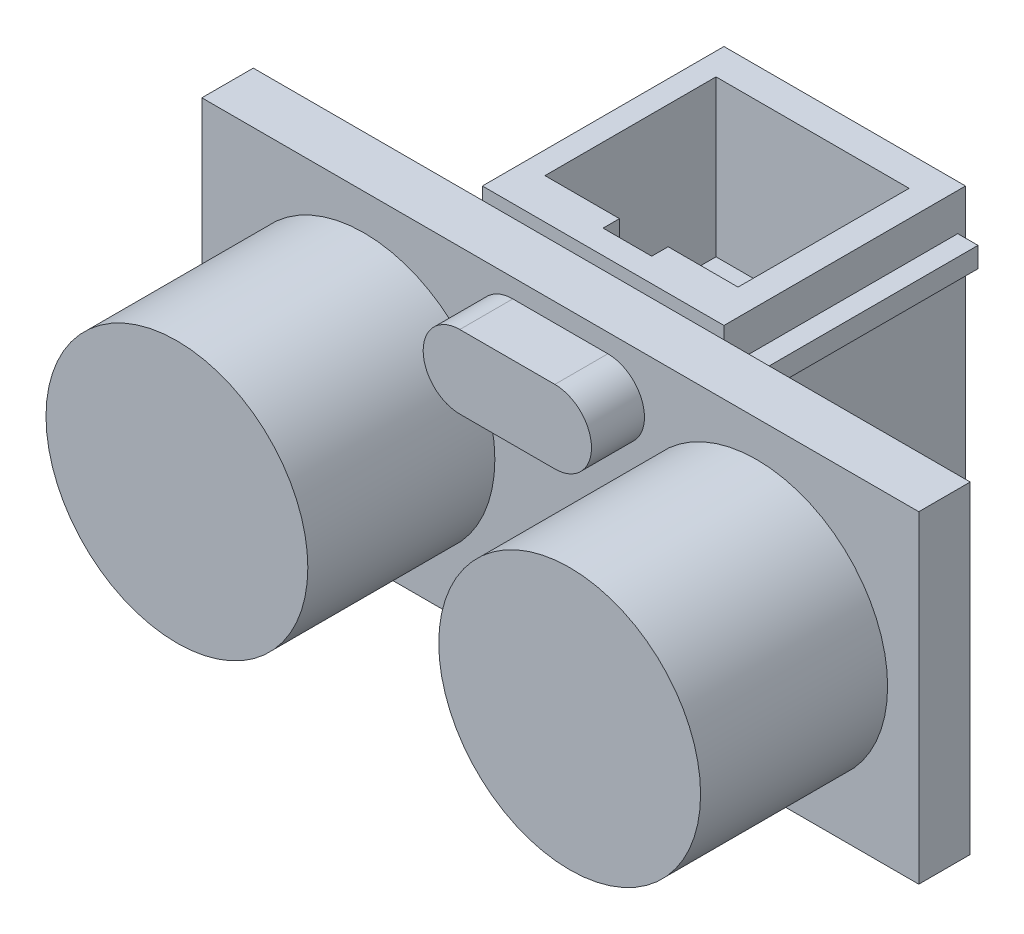
SolidWorks part; units mm, degrees
ref_plane "Front Plane" through (0, 0, 0) normal (0, 0, 1) x (1, 0, 0)
ref_plane "Top Plane" through (0, 0, 0) normal (0, 1, 0) x (1, 0, 0)
ref_plane "Right Plane" through (0, 0, 0) normal (1, 0, 0) x (0, 0, -1)
sketch "Sketch1" plane through (0, 0, 0) normal (0, 0, 1) x (1, 0, 0)
  line L1 (-23, -10.35) -> (23, -10.35)
  line L2 (-23, -10.35) -> (-23, 10.35)
  line L3 (-23, 10.35) -> (23, 10.35)
  line L4 (23, -10.35) -> (23, 10.35)
  line L5 (-23, -10.35) -> (23, 10.35) construction
  line L6 (-23, 10.35) -> (23, -10.35) construction
  point P0 (0, 0)
  dimension "D1" = 46
  dimension "D2" = 20.7
extrude "Boss-Extrude1" add sketch "Sketch1" along normal blind 3.3
sketch "Sketch2" plane through (0, 0, 3.3) normal (0, 0, 1) x (1, 0, 0)
  line L0 (-23, -0.35) -> (23, -0.35) construction
  line L1 (-23, 10.35) -> (-23, -10.35) construction
  line L2 (23, -10.35) -> (23, 10.35) construction
  line L3 (0, 0) -> (0, -0.35) construction
  line L4 (-12.6, -0.35) -> (0, 0) construction
  line L5 (0, 0) -> (12.6, -0.35) construction
  line L6 (23, 10.35) -> (-23, 10.35) construction
  circle A0 centre (-12.6, -0.35) radius 8.4
  circle A1 centre (12.6, -0.35) radius 8.4
  dimension "D1" = 25.2
  dimension "D2" = 16.8
  dimension "D3" = 10.7
extrude "Boss-Extrude2" add sketch "Sketch2" along normal blind 12
sketch "Sketch3" plane through (0, 0, 3.3) normal (0, 0, 1) x (1, 0, 0)
  line L0 (0, 0) -> (0, 13.591) construction
  line L1 (-3.05, 6.8) -> (3.05, 6.8) construction
  line L2 (-3.05, 9.15) -> (3.05, 9.15)
  line L3 (-3.05, 4.45) -> (3.05, 4.45)
  line L4 (23, 10.35) -> (-23, 10.35) construction
  arc A0 (-3.05, 9.15) -> (-3.05, 4.45) centre (-3.05, 6.8) ccw
  arc A1 (3.05, 4.45) -> (3.05, 9.15) centre (3.05, 6.8) ccw
  point P5 (0, 6.8)
  dimension "D3" = 10.8
  dimension "D1" = 1.2
  dimension "D2" = 4.7
extrude "Boss-Extrude3" add sketch "Sketch3" along normal blind 3.4
sketch "Sketch4" plane through (0, 0, 0) normal (0, 0, -1) x (-1, 0, 0)
  line L0 (23, -10.35) -> (-23, -10.35) construction
  line L1 (-7.2, 11.15) -> (8.3, 11.15)
  line L2 (-7.2, 11.15) -> (-7.2, -10.35)
  line L3 (-7.2, -10.35) -> (8.3, -10.35)
  line L4 (8.3, 11.15) -> (8.3, -10.35)
  line L5 (-23, 10.35) -> (23, 10.35) construction
  line L6 (-23, -10.35) -> (-23, 10.35) construction
  dimension "D1" = 0.8
  dimension "D2" = 15.5
  dimension "D3" = 15.8
extrude "Boss-Extrude4" add sketch "Sketch4" along normal blind 15.5
sketch "Sketch5" plane through (7.2, 0, 0) normal (1, 0, 0) x (0, 0, -1)
  line L0 (2.7, -10.35) -> (15.5, -6.45)
  line L1 (15.5, -10.35) -> (0, -10.35) construction
  line L2 (15.5, -6.45) -> (17.7624, -10.35)
  line L3 (17.7624, -10.35) -> (2.7, -10.35)
  line L4 (15.5, 11.15) -> (15.5, -10.35) construction
  dimension "D1" = 6
  dimension "D2" = 17.6
extrude "Cut-Extrude1" cut sketch "Sketch5" against normal through all
sketch "Sketch6" plane through (7.2, 0, 0) normal (1, 0, 0) x (0, 0, -1)
  line L0 (15.5, 11.15) -> (0, 11.15) construction
  line L1 (1, 8.75) -> (15, 8.75)
  line L2 (1, 8.75) -> (1, 7.45)
  line L3 (1, 7.45) -> (15, 7.45)
  line L4 (15, 8.75) -> (15, 7.45)
  line L5 (15.5, 11.15) -> (15.5, -6.45) construction
  line L6 (0, 10.35) -> (0, -10.35) construction
  dimension "D1" = 1.3
  dimension "D2" = 2.4
  dimension "D3" = 0.5
  dimension "D4" = 1
extrude "Boss-Extrude5" add sketch "Sketch6" along normal blind 1.3
sketch "Sketch7" plane through (-8.3, 0, 0) normal (-1, 0, 0) x (0, 0, 1)
  line L4 (-1, 8.75) -> (-15, 8.75)
  line L5 (-15, 8.75) -> (-15, 7.45)
  line L6 (-15, 7.45) -> (-1, 7.45)
  line L7 (-1, 7.45) -> (-1, 8.75)
  line L8 (-1, 8.75) -> (-15, 8.75)
  line L9 (-15, 8.75) -> (-15, 7.45)
  line L10 (-15, 7.45) -> (-1, 7.45)
  line L11 (-1, 7.45) -> (-1, 8.75)
  dimension "D1" = 0
extrude "Boss-Extrude6" add sketch "Sketch7" along normal blind 1.3
sketch "Sketch8" plane through (0, 11.15, 0) normal (0, 1, 0) x (1, 0, 0)
  line L0 (-0.55, 15.5) -> (-0.55, 0) construction
  line L1 (-8.3, 15.5) -> (7.2, 15.5) construction
  line L2 (7.2, 0) -> (-8.3, 0) construction
  line L4 (-6.8679, 2.5824) -> (5.5214, 2.5824)
  line L5 (-6.8679, 2.5824) -> (-6.8679, 13.5585)
  line L6 (-6.8679, 13.5585) -> (5.5214, 13.5585)
  line L7 (5.5214, 2.5824) -> (5.5214, 13.5585)
  line L8 (-2.086, 13.5585) -> (1.0353, 13.5585)
  line L9 (-2.086, 13.5585) -> (-2.086, 1.5297)
  line L10 (-2.086, 1.5297) -> (1.0353, 1.5297)
  line L11 (1.0353, 13.5585) -> (1.0353, 1.5297)
  point P5 (1.0353, 12.9176)
  point P16 (5.5214, 13.5585)
extrude "Cut-Extrude2" cut sketch "Sketch8" against normal blind 10 contours L9 L6 L5 L4 | L8 L0 L4 L11 | L0 L6 L9 L4 | L0 L4 L9 L10 | L4 L0 L10 L11 | L6 L11 L4 L7 region at (0.2426, 11.15, -8.0704) region at (-1.318, 11.15, -8.0704) region at (0.2426, 11.15, -2.056) region at (-1.318, 11.15, -2.056) region at (-4.4769, 11.15, -8.0704) region at (3.2783, 11.15, -8.0704)
